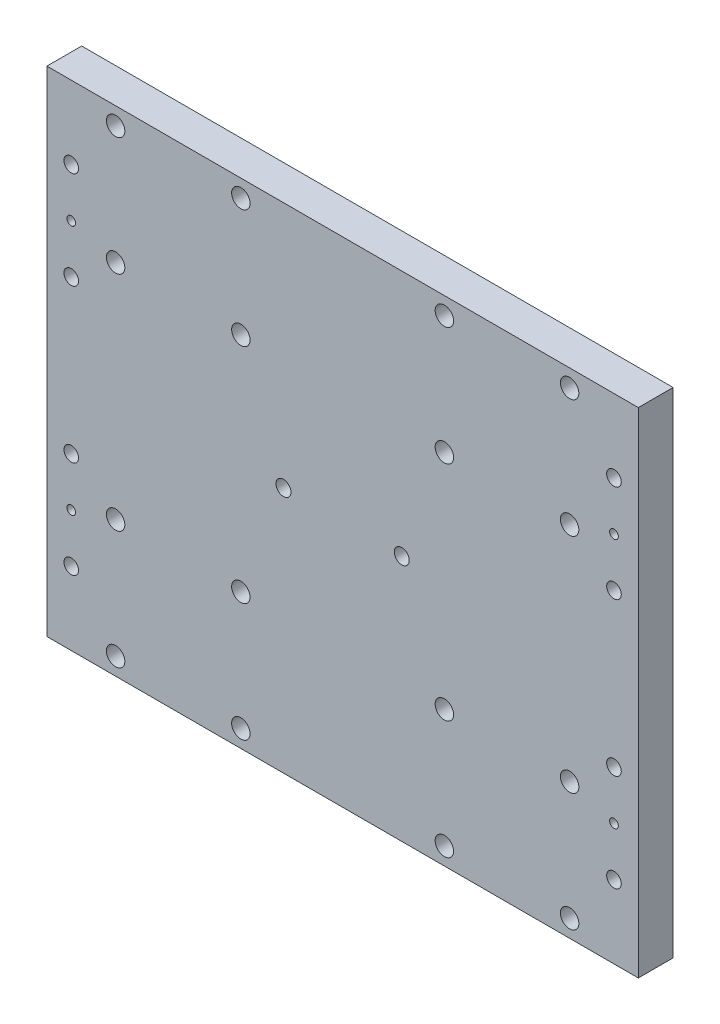
SolidWorks part; units mm, degrees
ref_plane "Front Plane" through (0, 0, 0) normal (0, 0, 1) x (1, 0, 0)
ref_plane "Top Plane" through (0, 0, 0) normal (0, 1, 0) x (1, 0, 0)
ref_plane "Right Plane" through (0, 0, 0) normal (1, 0, 0) x (0, 0, -1)
sketch "Sketch1" plane through (0, 0, 0) normal (0, 0, 1) x (1, 0, 0)
  line L1 (85, -71) -> (-85, -71)
  line L2 (85, -71) -> (85, 71)
  line L3 (85, 71) -> (-85, 71)
  line L4 (-85, -71) -> (-85, 71)
  line L5 (85, -71) -> (-85, 71) construction
  line L6 (85, 71) -> (-85, -71) construction
  point P0 (0, 0)
  dimension "D1" = 170
  dimension "D2" = 142
extrude "Boss-Extrude1" add sketch "Sketch1" along normal mid plane 10
hole_wizard "M5 Clearance Hole1" positions "Sketch8" profile "Sketch7" hole size "M5" standard "ANSI Metric" end condition through all
sketch "Sketch8" plane through (0, 0, 5) normal (0, 0, 1) x (1, 0, 0)
  line L1 (-29.25, 32) -> (-65.25, 32) construction
  line L2 (-29.25, 32) -> (-29.25, 66) construction
  line L3 (-29.25, 66) -> (-65.25, 66) construction
  line L4 (-65.25, 32) -> (-65.25, 66) construction
  line L5 (-29.25, 32) -> (-65.25, 66) construction
  line L6 (-29.25, 66) -> (-65.25, 32) construction
  line L9 (85, 71) -> (-85, 71) construction
  line L10 (-85, 71) -> (-85, -71) construction
  point P0 (-65.25, 66)
  point P2 (-29.25, 66)
  point P4 (-29.25, 32)
  point P6 (-65.25, 32)
  dimension "D1" = 5
  dimension "D2" = 19.75
  dimension "D3" = 34
  dimension "D4" = 36
sketch "Sketch7" plane through (-65.25, 66, 5) normal (1, 0, 0) x (0, -1, 0)
  line L0 (0, 0) -> (0, 10)
  line L1 (0, 10) -> (2.65, 10)
  line L2 (2.65, 10) -> (2.65, 0)
  line L5 (2.65, 0) -> (0, 0)
  line L11 (0, -6.35) -> (0, 107.95) construction
  dimension "Thru Hole Dia." = 5.3
  dimension "Thru Hole Depth" = 10
mirror "Mirror2" about plane through (0, 0, 0) normal (0, 1, 0) of "M5 Clearance Hole1"
mirror "Mirror3" about plane through (0, 0, 0) normal (1, 0, 0) of "Mirror2"
hole_wizard "M4 Clearance Hole1" positions "Sketch10" profile "Sketch9" hole size "M4" standard "ANSI Metric" end condition through all
sketch "Sketch10" plane through (0, 0, 5) normal (0, 0, 1) x (1, 0, 0)
  line L0 (-1000, 0) -> (49000, 0) construction
  point P0 (-17, 0)
  point P2 (17, 0)
  dimension "D1" = 17
  dimension "D2" = 17
sketch "Sketch9" plane through (-17, 0, 5) normal (1, 0, 0) x (0, -1, 0)
  line L0 (0, 0) -> (0, 10)
  line L1 (0, 10) -> (2.15, 10)
  line L2 (2.15, 10) -> (2.15, 0)
  line L5 (2.15, 0) -> (0, 0)
  line L11 (0, -6.35) -> (0, 107.95) construction
  dimension "Thru Hole Dia." = 4.3
  dimension "Thru Hole Depth" = 10
hole_wizard "M5x0.8 Tapped Hole1" positions "Sketch12" profile "Sketch11" tap size "M5x0.8" standard "ANSI Metric"
sketch "Sketch12" plane through (0, 0, 5) normal (0, 0, 1) x (1, 0, 0)
  line L0 (-78, -1023.3996) -> (-78, 48976.6004) construction
  line L1 (-85, 71) -> (-85, -71) construction
  line L2 (-1000, 0) -> (49000, 0) construction
  point P0 (-78, 50)
  point P2 (-78, 22)
  dimension "D1" = 7
  dimension "D2" = 22
  dimension "D3" = 50
sketch "Sketch11" plane through (-78, 50, 5) normal (1, 0, 0) x (0, -1, 0)
  line L0 (0, 0) -> (0, 15.2618)
  line L1 (0, 15.2618) -> (2.1, 14)
  line L2 (2.1, 14) -> (2.1, 0)
  line L5 (2.1, 0) -> (0, 0)
  line L10 (0, 15.2618) -> (-2.1, 14) construction
  line L11 (0, -6.35) -> (0, 107.95) construction
  dimension "Tap Drill Dia." = 4.2
  dimension "Tap Drill Depth" = 14
  dimension "Drill Angle" = 118
cosmetic thread "Hole Thread1" parameters "D1"=10, "D2"=5
cosmetic thread "Hole Thread2" parameters "D1"=10, "D2"=5
sketch "Sketch6" plane through (0, 0, 5) normal (0, 0, 1) x (1, 0, 0)
  line L0 (-78, -1002.1032) -> (-78, 48997.8968) construction
  line L1 (78, -1010.3548) -> (78, 48989.6452) construction
  line L2 (-85, 71) -> (-85, -71) construction
  line L3 (85, -71) -> (85, 71) construction
  line L6 (-1000, 0) -> (49000, 0) construction
  circle A1 centre (-78, 36) radius 1.25
  dimension "D4" = 2.5
  dimension "D1" = 7
  dimension "D2" = 7
  dimension "D10" = 36
extrude "Cut-Extrude5" cut sketch "Sketch6" against normal through all
mirror "Mirror1" about plane through (0, 0, 0) normal (1, 0, 0) of "M5x0.8 Tapped Hole1", "Cut-Extrude5"
mirror "Mirror4" about plane through (0, 0, 0) normal (0, 1, 0) of "Mirror1"
